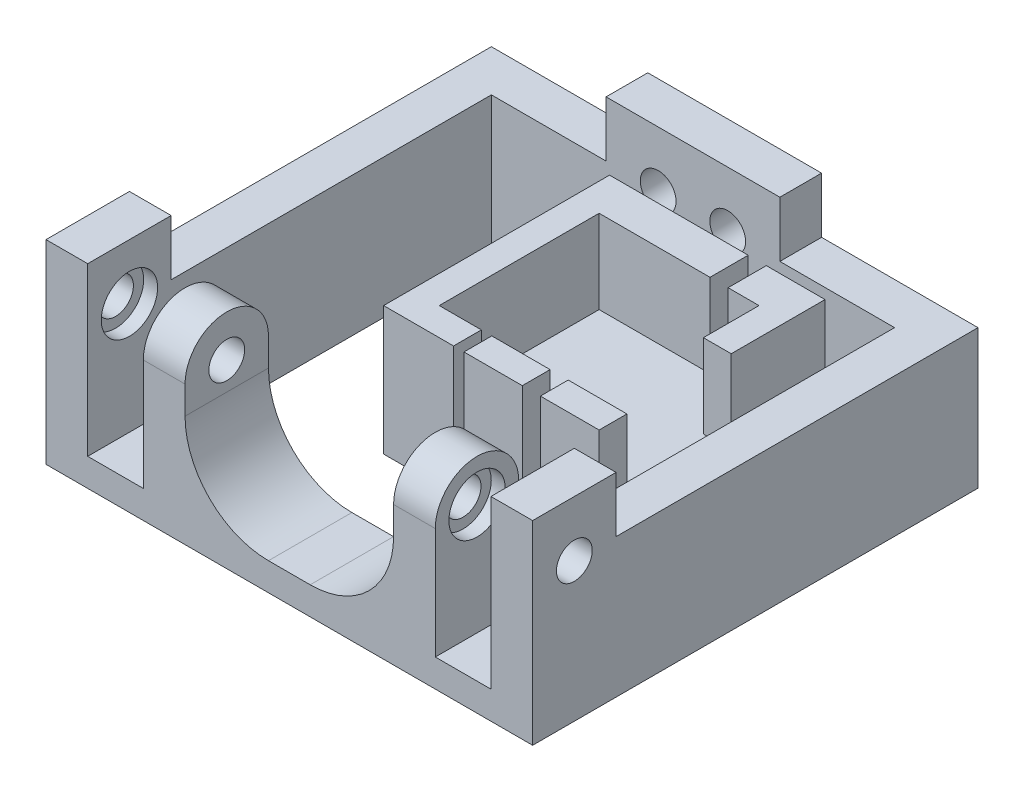
SolidWorks part; units mm, degrees
ref_plane "Front Plane" through (0, 0, 0) normal (0, 0, 1) x (1, 0, 0)
ref_plane "Top Plane" through (0, 0, 0) normal (0, 1, 0) x (1, 0, 0)
ref_plane "Right Plane" through (0, 0, 0) normal (1, 0, 0) x (0, 0, -1)
sketch "Sketch1" plane through (0, 0, 0) normal (0, 1, 0) x (1, 0, 0)
  line L0 (-29, 39) -> (-29, -39)
  line L1 (-35, 45) -> (35, 45)
  line L2 (-35, 45) -> (-35, -45)
  line L3 (-35, -45) -> (35, -45)
  line L4 (35, 45) -> (35, -45)
  line L5 (-29, -39) -> (29, -39)
  line L6 (29, 39) -> (29, -39)
  line L7 (-29, 39) -> (29, 39)
  point P4 (0, 45)
  point P5 (35, 0)
  point P7 (35, 27.1086)
  dimension "D1" = 70
  dimension "D2" = 90
  dimension "D3" = 6
extrude "Boss-Extrude1" add sketch "Sketch1" against normal blind 20
sketch "Sketch2" plane through (0, 0, 0) normal (0, -1, 0) x (-1, 0, 0)
  line L0 (-35, 45) -> (35, 45) construction
  line L1 (-12.5, 45) -> (12.5, 45)
  line L2 (-12.5, 45) -> (-12.5, 39)
  line L3 (-12.5, 39) -> (12.5, 39)
  line L4 (12.5, 45) -> (12.5, 39)
  line L5 (-29, 39) -> (29, 39) construction
  point P8 (0, 45)
  point P9 (0, 45)
  dimension "D1" = 25
extrude "Boss-Extrude2" add sketch "Sketch2" against normal blind 8
sketch "Sketch3" plane through (0, 0, -45) normal (0, 0, -1) x (-1, 0, 0)
  line L0 (0, 8) -> (0, 0) construction
  line L1 (12.5, 8) -> (-12.5, 8) construction
  circle A0 centre (-5, 0) radius 2.575
  circle A1 centre (5, 0) radius 2.575
  point P7 (0, 0)
  point P9 (-3.0953, 7.2588)
  point P14 (-18.5119, -15)
  dimension "D1" = 5.15
  dimension "D2" = 5
extrude "Cut-Extrude1" cut sketch "Sketch3" against normal up to next
sketch "Sketch4" plane through (0, 0, -45) normal (0, 0, -1) x (-1, 0, 0)
  line L0 (0, 0) -> (0, 8) construction
  line L1 (-35, 0) -> (35, 0) construction
  line L2 (12.5, 8) -> (-12.5, 8) construction
  circle A0 centre (-5, 0) radius 4.05
  circle A1 centre (-5, 0) radius 2.575 construction
  circle A2 centre (5, 0) radius 4.05
  dimension "D1" = 8.1
extrude "Cut-Extrude2" cut sketch "Sketch4" against normal blind 2
sketch "Sketch5" plane through (0, -20, 0) normal (0, 1, 0) x (1, 0, 0)
  line L0 (29, 39) -> (-29, 39) construction
  line L1 (-8, 33.5) -> (15, 33.5)
  line L2 (-8, 33.5) -> (-8, 10.5)
  line L3 (-8, 10.5) -> (15, 10.5)
  line L4 (15, 33.5) -> (15, 10.5)
  line L6 (29, -39) -> (29, 39) construction
  dimension "D1" = 23
  dimension "D2" = 23
  dimension "D3" = 5.5
  dimension "D4" = 14
extrude "Boss-Extrude3" add sketch "Sketch5" along normal offset from surface (6.5 mm away) 13.5 separate body up to face at (0, 0, -14)
sketch "Sketch16" plane through (0, -20, 0) normal (0, -1, 0) x (1, 0, 0)
  line L0 (29, -39) -> (12.5, -39) construction
  line L1 (19, -39) -> (-12, -39)
  line L2 (19, -39) -> (19, -6.5)
  line L3 (19, -6.5) -> (-12, -6.5)
  line L4 (-8, -33.5) -> (15, -33.5)
  line L5 (-8, -10.5) -> (-8, -33.5)
  line L6 (15, -10.5) -> (-8, -10.5)
  line L7 (15, -33.5) -> (15, -10.5)
  line L8 (-8, -33.5) -> (15, -33.5)
  line L9 (-8, -10.5) -> (-8, -33.5)
  line L10 (15, -10.5) -> (-8, -10.5)
  line L11 (15, -33.5) -> (15, -10.5)
  line L12 (-12, -39) -> (-12, -6.5)
  dimension "D2" = 4
  dimension "D3" = 4
  dimension "D4" = 4
  dimension "D1" = 0
extrude "Boss-Extrude6" add sketch "Sketch16" against normal offset from surface (18.5 mm away) 12 up to face at (3.5, -13.5, -22) offset beyond the face yes
sketch "gear_alignment_sketch" plane through (35, 0, 0) normal (1, 0, 0) x (0, 0, -1)
  line L0 (16.5, 0) -> (16.5, -20) construction
  line L1 (-45, 0) -> (45, 0) construction
  line L2 (-45, -20) -> (45, -20) construction
  line L3 (-992.2945, 0) -> (49007.7055, 0) construction
  line L5 (-45, 0) -> (45, 0) construction
  line L7 (-13.0635, 0) -> (16.5, -7.5) construction
  line L8 (10.5, -13.5) -> (33.5, -13.5) construction
  point P7 (-13.0635, 0)
  point P10 (16.5, -7.5)
  point P11 (0, 0)
  dimension "D1" = 6
  dimension "D3" = 30.5
  dimension "D2" = 6
sketch "Sketch8" plane through (0, 0, 0) normal (0, 1, 0) x (1, 0, 0)
  line L0 (35, -200992.2945) -> (35, 249007.7055) construction
  line L1 (35, -7.0635) -> (29, -7.0635)
  line L2 (35, -7.0635) -> (35, -19.0635)
  line L3 (35, -19.0635) -> (29, -19.0635)
  line L4 (29, -7.0635) -> (29, -19.0635)
  line L5 (29, -39) -> (29, 39) construction
  dimension "D1" = 12
extrude "Boss-Extrude4" add sketch "Sketch8" along normal blind 8
sketch "Sketch7" plane through (35, 0, 0) normal (1, 0, 0) x (0, 0, -1)
  circle A0 centre (-13.0635, 0) radius 2.575
  dimension "D1" = 5.15
extrude "x" cut sketch "Sketch7" against normal up to next
sketch "Sketch9" plane through (29, 0, 0) normal (1, 0, 0) x (0, 0, -1)
  circle A0 centre (-13.0635, 0) radius 4.05
  dimension "D1" = 8.1
extrude "Cut-Extrude4" cut sketch "Sketch9" along normal blind 2
sketch "Sketch10" plane through (0, -20, 0) normal (0, -1, 0) x (1, 0, 0)
  line L1 (0, 7.0635) -> (29, 7.0635)
  line L3 (0, 19.0635) -> (29, 19.0635)
  line L4 (29, 7.0635) -> (29, 19.0635)
  line L5 (29, 39) -> (29, -39) construction
  line L6 (35, 7.0635) -> (29, 7.0635) construction
  line L7 (29, 19.0635) -> (35, 19.0635) construction
  line L8 (0, -1000) -> (0, 49000) construction
  line L9 (0, 7.0635) -> (0, 19.0635)
extrude "Boss-Extrude5" add sketch "Sketch10" against normal up to surface (28 mm away) up to face at (32, 8, 13.0635)
sketch "Sketch12" plane through (0, 8, 0) normal (0, 1, 0) x (1, 0, 0)
  line L0 (0, -19.0635) -> (35, -19.0635) construction
  line L1 (29, -7.0635) -> (21, -7.0635)
  line L2 (29, -7.0635) -> (29, -19.0635)
  line L3 (29, -19.0635) -> (21, -19.0635)
  line L4 (21, -7.0635) -> (21, -19.0635)
  line L5 (35, -7.0635) -> (0, -7.0635) construction
  line L6 (15, -7.0635) -> (0, -7.0635)
  line L7 (15, -7.0635) -> (15, -19.0635)
  line L8 (15, -19.0635) -> (0, -19.0635)
  line L9 (0, -7.0635) -> (0, -19.0635)
  dimension "D1" = 8
  dimension "D2" = 6
extrude "Cut-Extrude6" cut sketch "Sketch12" against normal blind 24
sketch "Sketch13" plane through (21, 0, 0) normal (1, 0, 0) x (0, 0, -1)
  circle A0 centre (-13.0635, 0) radius 2.575
  circle A1 centre (-13.0635, 0) radius 2.575 construction
extrude "Cut-Extrude7" cut sketch "Sketch13" against normal up to next
sketch "Sketch14" plane through (21, 0, 0) normal (1, 0, 0) x (0, 0, -1)
  circle A0 centre (-13.0635, 0) radius 4.05
  circle A1 centre (-13.0635, 0) radius 4.05 construction
extrude "Cut-Extrude8" cut sketch "Sketch14" against normal blind 2
sketch "Sketch15" plane through (21, 0, 0) normal (1, 0, 0) x (0, 0, -1)
  line L0 (-7.0635, 8) -> (-7.0635, 0) construction
  line L1 (-19.0635, 0) -> (-19.0635, 8)
  line L2 (-19.0635, 8) -> (-7.0635, 8)
  line L3 (-7.0635, 8) -> (-7.0635, 0)
  arc A0 (-19.0635, 0) -> (-7.0635, 0) centre (-13.0635, 0) cw
extrude "Cut-Extrude9" cut sketch "Sketch15" against normal up to next
fillet "Fillet1" radius 12 1 edges at (15, -16, 13.0635) type face fillet first side face at (7.5, -16, 13.0635) second side face at (15, 0, 10.4885)
mirror "Mirror1" about plane through (0, 0, 0) normal (1, 0, 0) of "Fillet1", "Cut-Extrude9", "Cut-Extrude8", "Cut-Extrude7", "Cut-Extrude6", "Boss-Extrude5", "Boss-Extrude4", "x", "Cut-Extrude4"
sketch "Sketch18" plane through (0, -1.5, 0) normal (0, 1, 0) x (1, 0, 0)
  line L0 (15, 33.5) -> (-8, 33.5) construction
  line L1 (7.95, 33.5) -> (10.55, 33.5)
  line L2 (7.95, 33.5) -> (7.95, 39)
  line L3 (7.95, 39) -> (10.55, 39)
  line L4 (10.55, 33.5) -> (10.55, 39)
  line L5 (7.093, 39) -> (19, 39) construction
  line L6 (19, 6.5) -> (-12, 6.5) construction
  line L7 (7.95, 6.5) -> (10.55, 6.5)
  line L8 (7.95, 6.5) -> (7.95, 10.5)
  line L9 (7.95, 10.5) -> (10.55, 10.5)
  line L10 (10.55, 6.5) -> (10.55, 10.5)
  line L11 (-8, 10.5) -> (15, 10.5) construction
  line L12 (15, 10.5) -> (-8, 10.5) construction
  line L13 (-1.939, 6.5) -> (-0.439, 6.5)
  line L14 (-1.939, 6.5) -> (-1.939, 10.5)
  line L15 (-1.939, 10.5) -> (-0.439, 10.5)
  line L16 (-0.439, 6.5) -> (-0.439, 10.5)
  line L17 (19, 39) -> (19, 6.5) construction
  line L18 (15, 10.5) -> (19, 10.5)
  line L19 (15, 10.5) -> (15, 25.5)
  line L20 (15, 25.5) -> (19, 25.5)
  line L21 (19, 10.5) -> (19, 25.5)
  line L22 (15, 10.5) -> (15, 33.5) construction
  point P31 (7.95, 36.25)
  dimension "D1" = 15
  dimension "D2" = 4.45
  dimension "D3" = 2.6
  dimension "D4" = 8.389
  dimension "D5" = 1.5
extrude "Cut-Extrude10" cut sketch "Sketch18" against normal up to surface (12 mm away) up to face at (3.5, -13.5, -22)
sketch "Sketch19" plane through (0, 0, 0) normal (0, 1, 0) x (1, 0, 0)
  line L1 (-35, -45) -> (35, -45)
  line L2 (-35, -45) -> (-35, -19.0635)
  line L3 (-35, -19.0635) -> (35, -19.0635)
  line L4 (35, -45) -> (35, -19.0635)
extrude "Cut-Extrude11" cut sketch "Sketch19" against normal through all
equation "\"bushing_hole_outer_diameter\"= 8.1mm"
equation "\"bushing_hole_inner_diameter\"= 5.15mm"
equation "\"D1@Sketch3\"=\"bushing_hole_inner_diameter\""
equation "\"D1@Sketch4\"=\"bushing_hole_outer_diameter\""
equation "\"bushing_flange_depth\"= 2mm"
equation "\"D1@Cut-Extrude2\"=\"bushing_flange_depth\""
equation "\"D1@Boss-Extrude3\"=12+1.5"
equation "\"gear_spacing\"= 30.5mm"
equation "\"D3@gear_alignment_sketch\" = \"gear_spacing\""
equation "\"D1@Sketch7\"=\"bushing_hole_inner_diameter\""
equation "\"D1@Sketch9\"=\"bushing_hole_outer_diameter\""
equation "\"D1@Cut-Extrude4\"=\"bushing_flange_depth\""
equation "\"D1@Cut-Extrude8\"=\"bushing_flange_depth\""
